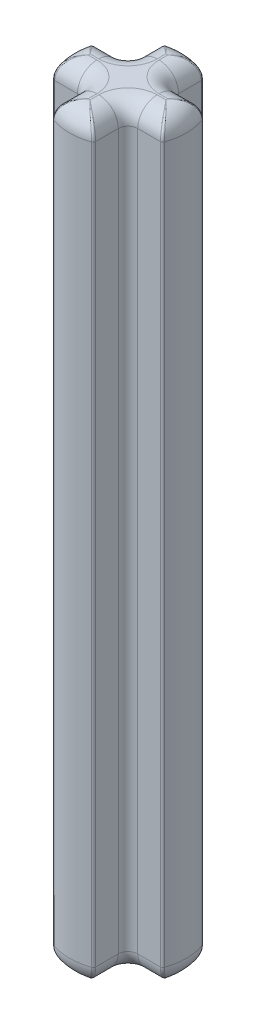
SolidWorks part; units mm, degrees
ref_plane "Front Plane" through (0, 0, 0) normal (0, 0, 1) x (1, 0, 0)
ref_plane "Top Plane" through (0, 0, 0) normal (0, 1, 0) x (1, 0, 0)
ref_plane "Right Plane" through (0, 0, 0) normal (1, 0, 0) x (0, 0, -1)
sketch "Sketch2" plane through (0, 0, 0) normal (0, 1, 0) x (1, 0, 0)
  line L0 (1.24, 0.84) -> (2.1777, 0.84)
  line L2 (-0.84, 2.1777) -> (-0.84, 1.24)
  line L4 (0.84, 2.1777) -> (0.84, 1.24)
  line L5 (-0.84, 2.2482) -> (0.84, -2.2482) construction
  line L6 (-0.84, -2.2482) -> (0.84, 2.2482) construction
  line L7 (-2.1777, 0.84) -> (-1.24, 0.84)
  line L9 (-2.1777, -0.84) -> (-1.24, -0.84)
  line L11 (-2.2482, 0.84) -> (2.2482, -0.84) construction
  line L12 (-2.2482, -0.84) -> (2.2482, 0.84) construction
  line L13 (1.24, -0.84) -> (2.1777, -0.84)
  line L14 (0.84, -1.24) -> (0.84, -2.1777)
  line L15 (-0.84, -1.24) -> (-0.84, -2.1777)
  arc A0 (-2.2724, 0.7722) -> (-2.2724, -0.7722) centre (0, 0) ccw
  arc A1 (0.7722, 2.2724) -> (-0.7722, 2.2724) centre (0, 0) ccw
  arc A2 (2.2724, -0.7722) -> (2.2724, 0.7722) centre (0, 0) ccw
  arc A3 (-0.7722, -2.2724) -> (0.7722, -2.2724) centre (0, 0) ccw
  arc A4 (2.1777, 0.84) -> (2.2724, 0.7722) centre (2.1777, 0.74) cw
  arc A5 (2.1777, -0.84) -> (2.2724, -0.7722) centre (2.1777, -0.74) ccw
  arc A6 (0.7722, -2.2724) -> (0.84, -2.1777) centre (0.74, -2.1777) ccw
  arc A7 (-0.84, -2.1777) -> (-0.7722, -2.2724) centre (-0.74, -2.1777) ccw
  arc A8 (-2.2724, -0.7722) -> (-2.1777, -0.84) centre (-2.1777, -0.74) ccw
  arc A9 (-2.1777, 0.84) -> (-2.2724, 0.7722) centre (-2.1777, 0.74) ccw
  arc A10 (0.7722, 2.2724) -> (0.84, 2.1777) centre (0.74, 2.1777) cw
  arc A11 (-0.7722, 2.2724) -> (-0.84, 2.1777) centre (-0.74, 2.1777) ccw
  arc A12 (-1.24, -0.84) -> (-0.84, -1.24) centre (-1.24, -1.24) cw
  arc A13 (1.24, -0.84) -> (0.84, -1.24) centre (1.24, -1.24) ccw
  arc A14 (1.24, 0.84) -> (0.84, 1.24) centre (1.24, 1.24) cw
  arc A15 (-1.24, 0.84) -> (-0.84, 1.24) centre (-1.24, 1.24) ccw
  point P40 (-0.84, -0.84)
  point P43 (0.84, -0.84)
  dimension "D1" = 4.8
  dimension "D4" = 0.1
  dimension "D5" = 0.4
  dimension "D2" = 1.68
  dimension "D3" = 1.68
extrude "Boss-Extrude1" add sketch "Sketch2" along normal blind 31
fillet "Fillet1" radius 0.8 24 edges at (0.8213, 31, -2.2359) (0.84, 31, -1.7089) (0.9572, 31, -0.9572) (1.7089, 31, -0.84) (2.2359, 31, -0.8213) (2.4, 31, 0) (2.2359, 31, 0.8213) (1.7089, 31, 0.84) (0.9572, 31, 0.9572) (0.84, 31, 1.7089) (0.8213, 31, 2.2359) (0, 31, 2.4) (-0.8213, 31, 2.2359) (-0.84, 31, 1.7089) (-0.9572, 31, 0.9572) (-1.7089, 31, 0.84) (-2.2359, 31, 0.8213) (-2.4, 31, 0) (-2.2359, 31, -0.8213) (-1.7089, 31, -0.84) (-0.9572, 31, -0.9572) (-0.84, 31, -1.7089) (-0.8213, 31, -2.2359) (0, 31, -2.4)
fillet "Fillet2" radius 0.8 24 edges at (-0.8213, 0, 2.2359) (-0.84, 0, 1.7089) (-0.9572, 0, 0.9572) (-1.7089, 0, 0.84) (-2.2359, 0, 0.8213) (-2.4, 0, 0) (-2.2359, 0, -0.8213) (-1.7089, 0, -0.84) (-0.9572, 0, -0.9572) (-0.84, 0, -1.7089) (-0.8213, 0, -2.2359) (0, 0, -2.4) (0.8213, 0, -2.2359) (0.84, 0, -1.7089) (0.9572, 0, -0.9572) (1.7089, 0, -0.84) (2.2359, 0, -0.8213) (2.4, 0, 0) (2.2359, 0, 0.8213) (1.7089, 0, 0.84) (0.9572, 0, 0.9572) (0.84, 0, 1.7089) (0.8213, 0, 2.2359) (0, 0, 2.4)
